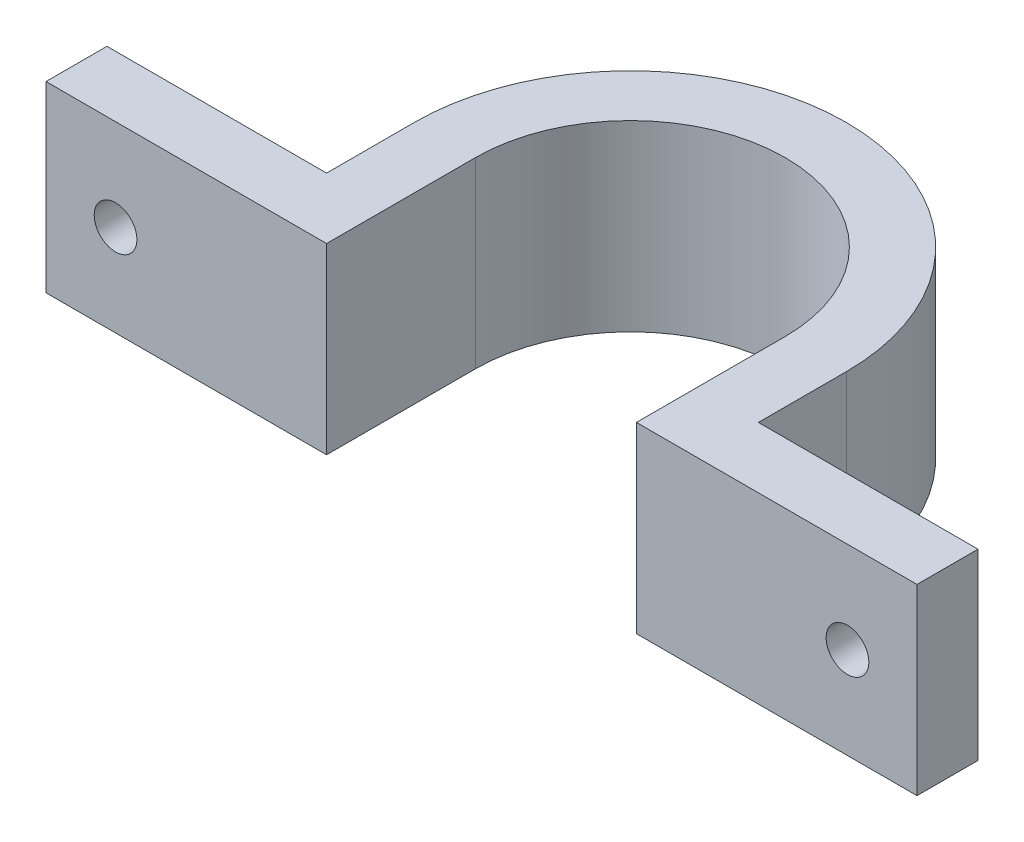
SolidWorks part; units mm, degrees
ref_plane "Front Plane" through (0, 0, 0) normal (0, 0, 1) x (1, 0, 0)
ref_plane "Top Plane" through (0, 0, 0) normal (0, 1, 0) x (1, 0, 0)
ref_plane "Right Plane" through (0, 0, 0) normal (1, 0, 0) x (0, 0, -1)
sketch "Sketch1" plane through (0, 0, 0) normal (0, 1, 0) x (1, 0, 0)
  line L6 (-35.7, -7.2) -> (-35.7, -12.2)
  line L7 (-35.7, -12.2) -> (-12.7, -12.2)
  line L8 (-12.7, -12.2) -> (-12.7, 0)
  line L10 (35.7, -7.2) -> (35.7, -12.2)
  line L11 (35.7, -12.2) -> (12.7, -12.2)
  line L12 (12.7, -12.2) -> (12.7, 0)
  line L14 (-17.7, 0) -> (-17.7, -7.2)
  line L15 (-17.7, -7.2) -> (-35.7, -7.2)
  line L16 (17.7, 0) -> (17.7, -7.2)
  line L17 (17.7, -7.2) -> (35.7, -7.2)
  arc A0 (17.7, 0) -> (-17.7, 0) centre (0, 0) ccw
  arc A1 (-12.7, 0) -> (12.7, 0) centre (0, 0) cw
  point P1 (0, 0)
  point P12 (0, -12.7)
  point P15 (-25.4, -23.842)
  dimension "D1" = 12.7
  dimension "D2" = 5
  dimension "D5" = 0.5
  dimension "D3" = 5
  dimension "D4" = 18
extrude "Boss-Extrude1" add sketch "Sketch1" along normal blind 15
sketch "Sketch2" plane through (0, 0, 7.2) normal (0, 0, -1) x (-1, 0, 0)
  line L0 (-35.7, 7.5) -> (-30, 7.5) construction
  line L2 (35.7, 7.5) -> (30, 7.5) construction
  line L4 (-35.7, 15) -> (-35.7, 0) construction
  line L5 (35.7, 15) -> (35.7, 0) construction
  circle A0 centre (-30, 7.5) radius 1.75
  circle A1 centre (30, 7.5) radius 1.75
  point P6 (-48.4, 5)
  point P9 (48.4, 5)
  dimension "D1" = 3.5
  dimension "D2" = 60
extrude "Cut-Extrude1" cut sketch "Sketch2" against normal through all
